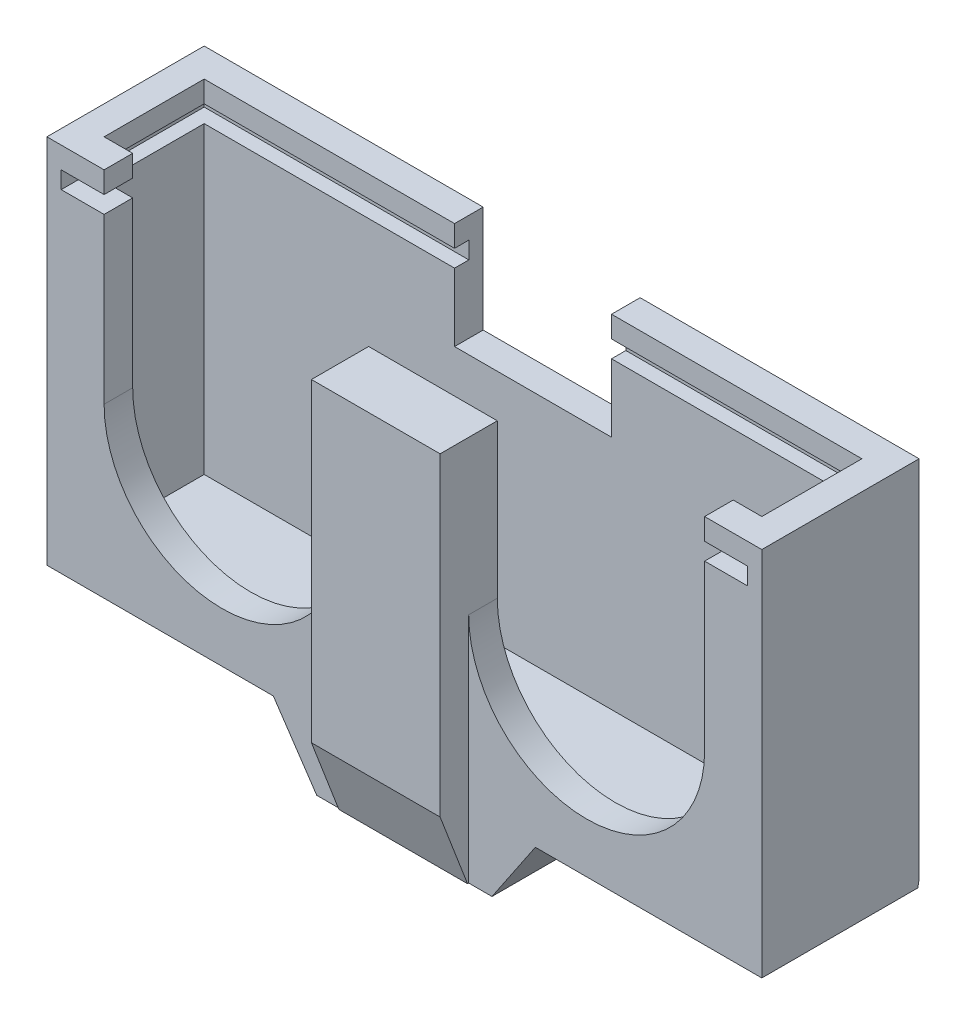
SolidWorks part; units mm, degrees
ref_plane "Plano frontal" through (0, 0, 0) normal (0, 0, 1) x (1, 0, 0)
ref_plane "Plano superior" through (0, 0, 0) normal (0, 1, 0) x (1, 0, 0)
ref_plane "Plano direito" through (0, 0, 0) normal (1, 0, 0) x (0, 0, -1)
sketch "Esboço1" plane through (0, 0, 0) normal (0, 1, 0) x (1, 0, 0)
  line L1 (-25, 5.5) -> (25, 5.5)
  line L2 (-25, 5.5) -> (-25, -5.5)
  line L3 (-25, -5.5) -> (25, -5.5)
  line L4 (25, 5.5) -> (25, -5.5)
  line L5 (-25, 5.5) -> (25, -5.5) construction
  line L6 (-25, -5.5) -> (25, 5.5) construction
  point P0 (0, 0)
  dimension "D1" = 50
  dimension "D2" = 11
extrude "Ressalto-extrusão1" add sketch "Esboço1" along normal blind 22.5
sketch "Esboço2" plane through (0, 22.5, 0) normal (0, 1, 0) x (1, 0, 0)
  line L1 (-23, 3.5) -> (23, 3.5)
  line L2 (-23, 3.5) -> (-23, -3.5)
  line L3 (-23, -3.5) -> (23, -3.5)
  line L4 (23, 3.5) -> (23, -3.5)
  line L5 (-23, 3.5) -> (23, -3.5) construction
  line L6 (-23, -3.5) -> (23, 3.5) construction
  point P0 (0, 0)
extrude "Corte-extrusão1" cut sketch "Esboço2" against normal blind 20.5
sketch "Esboço3" plane through (0, 22.5, 0) normal (0, 1, 0) x (1, 0, 0)
  line L3 (23, 3.5) -> (-23, 3.5) construction
  line L4 (-5.4896, 5.5) -> (5.4896, 5.5)
  line L5 (-5.4896, 5.5) -> (-5.4896, 3.5)
  line L6 (-5.4896, 3.5) -> (5.4896, 3.5)
  line L7 (5.4896, 5.5) -> (5.4896, 3.5)
  line L8 (-5.4896, 5.5) -> (5.4896, 3.5) construction
  line L9 (-5.4896, 3.5) -> (5.4896, 5.5) construction
  point P6 (0, 4.5)
extrude "Corte-extrusão2" cut sketch "Esboço3" against normal blind 4
sketch "Esboço5" plane through (0, 0, 5.5) normal (0, 0, 1) x (1, 0, 0)
  line L0 (-25, 22.5) -> (25, 22.5) construction
  line L1 (-21, 22.5) -> (-4.5, 22.5)
  line L2 (-21, 22.5) -> (-21, 11.75)
  line L4 (-4.5, 22.5) -> (-4.5, 11.75)
  line L5 (-25, 22.5) -> (-25, 0) construction
  line L7 (4.5, 22.5) -> (21, 22.5)
  line L8 (4.5, 22.5) -> (4.5, 11.75)
  line L10 (21, 22.5) -> (21, 11.75)
  line L11 (25, 22.5) -> (25, 0) construction
  arc A0 (-21, 11.75) -> (-4.5, 11.75) centre (-12.75, 11.75) ccw
  arc A1 (4.5, 11.75) -> (21, 11.75) centre (12.75, 11.75) ccw
  dimension "D1" = 16.5
  dimension "D2" = 4
  dimension "D3" = 16.5
  dimension "D4" = 4
  dimension "D6" = 0
extrude "Corte-extrusão3" cut sketch "Esboço5" against normal blind 4
sketch "Esboço9" plane through (0, 0, -5.5) normal (0, 0, -1) x (-1, 0, 0)
  line L0 (25, 22.5) -> (25, 0) construction
  line L1 (-25, 0) -> (25, 0)
  line L2 (-25, 0) -> (-25, 4)
  line L3 (-25, 4) -> (25, 4)
  line L4 (25, 0) -> (25, 4)
  dimension "D1" = 4
extrude "Ressalto-extrusão4" add sketch "Esboço9" along normal blind 7
sketch "Esboço13" plane through (0, 4, 0) normal (0, 1, 0) x (1, 0, 0)
  line L0 (25, 12.5) -> (25, 5.5) construction
  circle A0 centre (10, 9) radius 1.5
  circle A1 centre (5, 9) radius 1.5
  circle A2 centre (20, 9) radius 1.5
  circle A3 centre (15, 9) radius 1.5
  circle A4 centre (0, 9) radius 1.5
  circle A5 centre (-5, 9) radius 1.5
  circle A6 centre (-10, 9) radius 1.5
  circle A7 centre (-15, 9) radius 1.5
  circle A8 centre (-20, 9) radius 1.5
extrude "Corte-extrusão4" cut sketch "Esboço13" against normal blind 7
sketch "Esboço19" plane through (0, 22.5, 0) normal (0, 1, 0) x (1, 0, 0)
  line L0 (4.5, -3.5) -> (4.5, -5.5) construction
  line L1 (-4.5, -3.5) -> (4.5, -3.5)
  line L2 (-4.5, -3.5) -> (-4.5, -7.5)
  line L3 (-4.5, -7.5) -> (4.5, -7.5)
  line L4 (4.5, -3.5) -> (4.5, -7.5)
  point P4 (4.5, -4.5)
  dimension "D1" = 4
  dimension "D2" = 0
extrude "Ressalto-extrusão5" add sketch "Esboço19" against normal blind 22.5
sketch "Esboço20" plane through (0, 0, -12.5) normal (0, 0, -1) x (-1, 0, 0)
  line L4 (-25, 4) -> (-25, 0)
  line L5 (-25, 0) -> (25, 0)
  line L6 (25, 0) -> (25, 4)
  line L7 (25, 4) -> (-25, 4)
  line L8 (-25, 4) -> (-25, 0)
  line L9 (-25, 0) -> (25, 0)
  line L10 (25, 0) -> (25, 4)
  line L11 (25, 4) -> (-25, 4)
  dimension "D1" = 0
extrude "Corte-extrusão5" cut sketch "Esboço20" against normal up to vertex (7 mm away) up to point (25, 4, -5.5)
sketch "Esboço21" plane through (0, 22.5, 0) normal (0, 1, 0) x (1, 0, 0)
  line L0 (-21, -5.5) -> (-21, -3.5) construction
  line L1 (-21, -3.5) -> (-23, -3.5) construction
  line L2 (-23, -3.5) -> (-23, 3.5) construction
  line L3 (-23, 3.5) -> (-5.4896, 3.5) construction
  line L4 (-5.4896, 3.5) -> (-5.4896, 5.5) construction
  line L5 (-5.4896, 5.5) -> (-25, 5.5) construction
  line L6 (-25, 5.5) -> (-25, -5.5) construction
  line L7 (-25, -5.5) -> (-21, -5.5) construction
  line L8 (21, -3.5) -> (21, -5.5) construction
  line L9 (21, -5.5) -> (25, -5.5) construction
  line L10 (25, -5.5) -> (25, 5.5) construction
  line L11 (25, 5.5) -> (5.4896, 5.5) construction
  line L12 (5.4896, 5.5) -> (5.4896, 3.5) construction
  line L13 (5.4896, 3.5) -> (23, 3.5) construction
  line L14 (23, 3.5) -> (23, -3.5) construction
  line L15 (23, -3.5) -> (21, -3.5) construction
  line L16 (-21, -5.5) -> (-21, -3.5)
  line L17 (-21, -3.5) -> (-23, -3.5)
  line L18 (-23, -3.5) -> (-23, 3.5)
  line L19 (-23, 3.5) -> (-5.4896, 3.5)
  line L20 (-5.4896, 3.5) -> (-5.4896, 5.5)
  line L21 (-5.4896, 5.5) -> (-25, 5.5)
  line L22 (-25, 5.5) -> (-25, -5.5)
  line L23 (-25, -5.5) -> (-21, -5.5)
  line L24 (21, -3.5) -> (21, -5.5)
  line L25 (21, -5.5) -> (25, -5.5)
  line L26 (25, -5.5) -> (25, 5.5)
  line L27 (25, 5.5) -> (5.4896, 5.5)
  line L28 (5.4896, 5.5) -> (5.4896, 3.5)
  line L29 (5.4896, 3.5) -> (23, 3.5)
  line L30 (23, 3.5) -> (23, -3.5)
  line L31 (23, -3.5) -> (21, -3.5)
extrude "Ressalto-extrusão6" add sketch "Esboço21" along normal blind 0.75
sketch "Esboço22" plane through (0, 23.25, 0) normal (0, 1, 0) x (1, 0, 0)
  line L6 (-5.4896, 5.5) -> (-25, 5.5) construction
  line L7 (-25, 5.5) -> (-25, -5.5) construction
  line L11 (25, -5.5) -> (25, 5.5) construction
  line L12 (25, 5.5) -> (5.4896, 5.5) construction
  line L16 (-24, 3.5) -> (-24, -5.5)
  line L17 (-25, -5.5) -> (-21, -5.5) construction
  line L18 (-24, -5.5) -> (-25, -5.5)
  line L19 (-24, 4.5) -> (-23, 4.5)
  line L20 (-24, 4.5) -> (-24, 3.5)
  line L21 (-23, 4.5) -> (-5.4896, 4.5)
  line L22 (-5.4896, 5.5) -> (-25, 5.5)
  line L23 (-25, 5.5) -> (-25, -5.5)
  line L24 (-5.4896, 3.5) -> (-5.4896, 5.5) construction
  line L25 (-5.4896, 4.5) -> (-5.4896, 5.5)
  line L26 (23, 4.5) -> (5.4896, 4.5)
  line L27 (25, -5.5) -> (25, 5.5)
  line L28 (25, 5.5) -> (5.4896, 5.5)
  line L29 (5.4896, 5.5) -> (5.4896, 3.5) construction
  line L30 (5.4896, 4.5) -> (5.4896, 5.5)
  line L31 (23, 4.5) -> (24, 4.5)
  line L32 (-23, 3.5) -> (-24, 3.5) construction
  line L33 (-23, 3.5) -> (-23, 4.5) construction
  line L34 (23, 3.5) -> (24, 3.5) construction
  line L35 (23, 3.5) -> (23, 4.5) construction
  line L36 (24, 4.5) -> (24, 3.5)
  line L37 (24, 3.5) -> (24, -5.5)
  line L38 (21, -5.5) -> (25, -5.5) construction
  line L39 (24, -5.5) -> (25, -5.5)
extrude "Ressalto-extrusão7" add sketch "Esboço22" along normal blind 1.2
sketch "Esboço23" plane through (0, 24.45, 0) normal (0, 1, 0) x (1, 0, 0)
  line L0 (-25, 5.5) -> (-25, -5.5) construction
  line L1 (-25, -5.5) -> (-24, -5.5) construction
  line L4 (-5.4896, 4.5) -> (-5.4896, 5.5) construction
  line L5 (-5.4896, 5.5) -> (-25, 5.5) construction
  line L8 (24, -5.5) -> (25, -5.5) construction
  line L9 (25, -5.5) -> (25, 5.5) construction
  line L10 (25, 5.5) -> (5.4896, 5.5) construction
  line L11 (5.4896, 5.5) -> (5.4896, 4.5) construction
  line L12 (-5.4896, 4.5) -> (-24, 4.5) construction
  line L13 (-24, 4.5) -> (-24, -5.5) construction
  line L14 (-24, -5.5) -> (-21, -5.5) construction
  line L15 (-21, -5.5) -> (-21, -3.5) construction
  line L16 (-21, -3.5) -> (-23, -3.5) construction
  line L17 (-23, -3.5) -> (-23, 3.5) construction
  line L18 (-23, 3.5) -> (-5.4896, 3.5) construction
  line L19 (-5.4896, 3.5) -> (-5.4896, 4.5) construction
  line L20 (21, -5.5) -> (24, -5.5) construction
  line L21 (24, -5.5) -> (24, 4.5) construction
  line L22 (24, 4.5) -> (5.4896, 4.5) construction
  line L23 (5.4896, 4.5) -> (5.4896, 3.5) construction
  line L24 (5.4896, 3.5) -> (23, 3.5) construction
  line L25 (23, 3.5) -> (23, -3.5) construction
  line L26 (23, -3.5) -> (21, -3.5) construction
  line L27 (21, -3.5) -> (21, -5.5) construction
  line L28 (-25, 5.5) -> (-25, -5.5)
  line L29 (-25, -5.5) -> (-24, -5.5)
  line L32 (-5.4896, 4.5) -> (-5.4896, 5.5)
  line L33 (-5.4896, 5.5) -> (-25, 5.5)
  line L36 (24, -5.5) -> (25, -5.5)
  line L37 (25, -5.5) -> (25, 5.5)
  line L38 (25, 5.5) -> (5.4896, 5.5)
  line L39 (5.4896, 5.5) -> (5.4896, 4.5)
  line L40 (-5.4896, 4.5) -> (-24, 4.5)
  line L41 (-24, 4.5) -> (-24, -5.5)
  line L42 (-24, -5.5) -> (-21, -5.5)
  line L43 (-21, -5.5) -> (-21, -3.5)
  line L44 (-21, -3.5) -> (-23, -3.5)
  line L45 (-23, -3.5) -> (-23, 3.5)
  line L46 (-23, 3.5) -> (-5.4896, 3.5)
  line L47 (-5.4896, 3.5) -> (-5.4896, 4.5)
  line L48 (21, -5.5) -> (24, -5.5)
  line L49 (24, -5.5) -> (24, 4.5)
  line L50 (24, 4.5) -> (5.4896, 4.5)
  line L51 (5.4896, 4.5) -> (5.4896, 3.5)
  line L52 (5.4896, 3.5) -> (23, 3.5)
  line L53 (23, 3.5) -> (23, -3.5)
  line L54 (23, -3.5) -> (21, -3.5)
  line L55 (21, -3.5) -> (21, -5.5)
  line M1 (5.4896, 4.5) -> (24, 4.5)
  line M2 (24, 4.5) -> (24, -5.5)
  line M3 (24, -5.5) -> (25, -5.5)
  line M4 (25, -5.5) -> (25, 5.5)
  line M5 (25, 5.5) -> (5.4896, 5.5)
  line M6 (5.4896, 5.5) -> (5.4896, 4.5)
extrude "Ressalto-extrusão8" add sketch "Esboço23" along normal blind 1.5 contours L41 L40 L32 L33 L28 L29 | L46 L47 L40 L41 L42 L43 L44 L45 | M6 M1 M2 M3 M4 M5 | L54 L55 L48 L51 L52 L53 M2 M1 region at (-15.2448, 24.45, -5.276) region at (-23.7896, 24.45, 0.5) region at (24.224, 24.45, 0.5) region at (22.5, 24.45, 5.2896)
sketch "Esboço24" plane through (0, 0, 0) normal (0, -1, 0) x (1, 0, 0)
  line L0 (-25, 5.5) -> (25, -5.5) construction
  line L1 (25, 5.5) -> (-25, -5.5) construction
  line L2 (0, 0) -> (0, 3.5) construction
  line L3 (0, 0) -> (-3.5, 0) construction
  line L4 (0, 3.5) -> (-3.5, 3.5)
  line L5 (-3.5, 3.5) -> (-3.5, 0)
  line L6 (-3.5, 0) -> (-3.5, -3.5)
  line L7 (-3.5, -3.5) -> (3.5, -3.5)
  line L8 (3.5, -3.5) -> (3.5, 3.5)
  line L9 (3.5, 3.5) -> (0, 3.5)
extrude "Ressalto-extrusão9" add sketch "Esboço24" along normal blind 4.5
sketch "Esboço26" plane through (0, -4.5, 0) normal (0, -1, 0) x (1, 0, 0)
  circle A0 centre (0, 0) radius 2.9
extrude "Corte-extrusão6" cut sketch "Esboço26" against normal blind 4 contours A0
sketch "Esboço28" plane through (0, 0, 0) normal (0, -1, 0) x (1, 0, 0)
  line L0 (-4.5, 5.5) -> (-9.5, 5.5) construction
  line L1 (-9.5, 5.5) -> (-9.5, -5.5)
  line L2 (4.5, 5.5) -> (9.5, 5.5) construction
  line L3 (9.5, 5.5) -> (9.5, -5.5)
  line L4 (9.5, 5.5) -> (4.5, 5.5)
  line L5 (4.5, 7.5) -> (-4.5, 7.5)
  line L6 (-4.5, 5.5) -> (-9.5, 5.5)
  line L7 (-9.5, -5.5) -> (9.5, -5.5)
  line L8 (-25, -5.5) -> (25, -5.5)
  line L9 (25, -5.5) -> (25, 5.5)
  line L10 (25, 5.5) -> (4.5, 5.5)
  line L11 (4.5, 5.5) -> (4.5, 7.5)
  line L12 (4.5, 7.5) -> (-4.5, 7.5)
  line L13 (-4.5, 7.5) -> (-4.5, 5.5)
  line L14 (-4.5, 5.5) -> (-25, 5.5)
  line L15 (-25, 5.5) -> (-25, -5.5)
  line L16 (-25, -5.5) -> (25, -5.5)
  line L17 (25, -5.5) -> (25, 5.5)
  line L18 (25, 5.5) -> (4.5, 5.5)
  line L19 (4.5, 5.5) -> (4.5, 7.5)
  line L20 (4.5, 7.5) -> (-4.5, 7.5)
  line L21 (-4.5, 7.5) -> (-4.5, 5.5)
  line L22 (-4.5, 5.5) -> (-25, 5.5)
  line L23 (-25, 5.5) -> (-25, -5.5)
  line M11 (-25, -5.5) -> (25, -5.5)
  line M13 (25, 5.5) -> (4.5, 5.5)
  line M14 (4.5, 5.5) -> (4.5, 7.5)
  line M15 (4.5, 7.5) -> (-4.5, 7.5)
  line M16 (-4.5, 7.5) -> (-4.5, 5.5)
  line M17 (-4.5, 5.5) -> (-25, 5.5)
  line M19 (-3.5, 3.5) -> (3.5, 3.5)
  line M20 (3.5, 3.5) -> (3.5, -3.5)
  line M21 (3.5, -3.5) -> (-3.5, -3.5)
  line M22 (-3.5, -3.5) -> (-3.5, 3.5)
  dimension "D1" = 0
extrude "Ressalto-extrusão10" add sketch "Esboço28" along normal up to vertex (4.5 mm away) contours L3 L1 M13 M14 M15 M16 M17 M11 M22 M19 M20 M21 region at (-7, 0, 5.2698) up to point (-3.5, -4.5, -3.5)
chamfer "Chanfro1" distance 5 angle 34 1 edges at (-9.5, -4.5, 0) first distance on face at (-9.5, -2.25, 0)
chamfer "Chanfro2" distance 5 angle 34 1 edges at (9.5, -4.5, 0) first distance on face at (9.5, -2.25, 0)
chamfer "Chanfro3" distance 5 angle 10 1 edges at (0, -4.5, -5.5) first distance on face at (0, 13.1458, -5.5)
chamfer "Chanfro4" distance 5 angle 21 1 edges at (0, -4.5, 7.5) first distance on face at (0, 9, 7.5)
